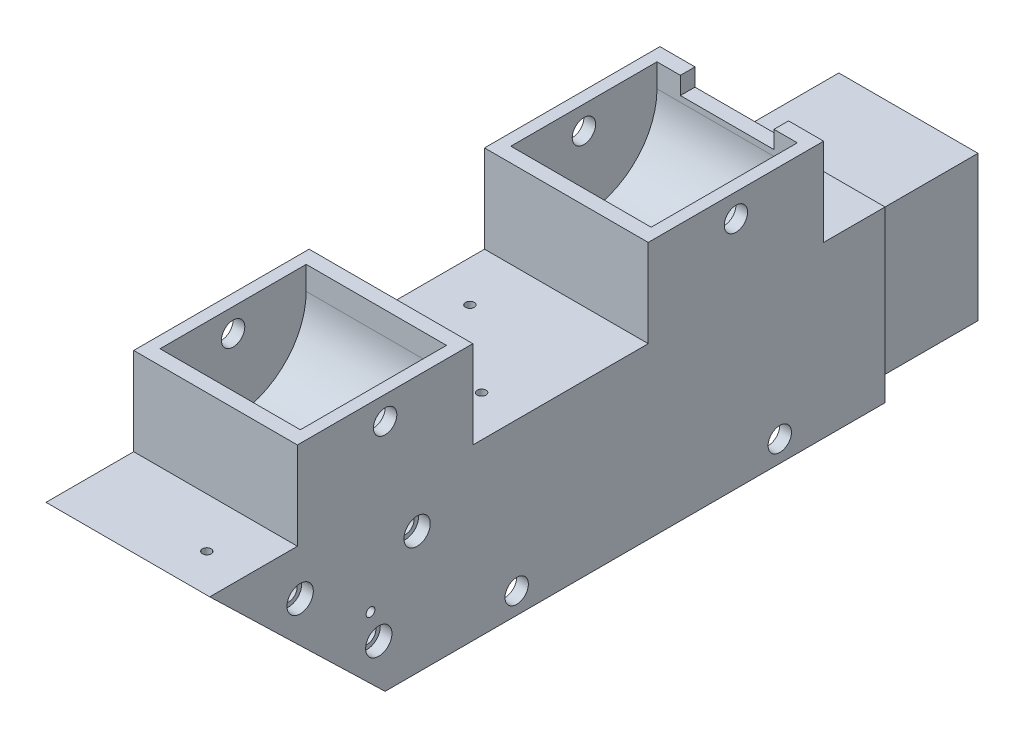
SolidWorks part; units mm, degrees
ref_plane "前视基准面" through (0, 0, 0) normal (0, 0, 1) x (1, 0, 0)
ref_plane "上视基准面" through (0, 0, 0) normal (0, 1, 0) x (1, 0, 0)
ref_plane "右视基准面" through (0, 0, 0) normal (1, 0, 0) x (0, 0, -1)
other "Configuration Table"
sketch "草图1" plane through (0, 0, 0) normal (1, 0, 0) x (0, 0, -1)
  line L0 (-150, 0) -> (150, 0) construction
  line L1 (-125, 14.5) -> (125, 14.5)
  line L2 (-125, 14.5) -> (-125, -14.5)
  line L3 (-125, -14.5) -> (125, -14.5)
  line L4 (125, 14.5) -> (125, -14.5)
  line L5 (-72.5, 29.5) -> (-72.5, 25.5)
  line L6 (-75, 14.5) -> (-45, 14.5)
  line L7 (-75, 14.5) -> (-75, 29.5)
  line L8 (-120, 10.8586) -> (120, 10.8586)
  line L9 (-120, 10.8586) -> (-120, -10.8586)
  line L10 (-120, -10.8586) -> (120, -10.8586)
  line L11 (120, 10.8586) -> (120, -10.8586)
  line L12 (-120, 10.8586) -> (120, -10.8586) construction
  line L13 (-120, -10.8586) -> (120, 10.8586) construction
  line L14 (-75, 29.5) -> (-45, 29.5)
  line L15 (-45, 14.5) -> (-45, 29.5)
  line L16 (-15, 14.5) -> (15, 14.5)
  line L17 (-15, 14.5) -> (-15, 29.5)
  line L18 (-15, 29.5) -> (15, 29.5)
  line L19 (15, 14.5) -> (15, 29.5)
  line L20 (45, 14.5) -> (75, 14.5)
  line L21 (45, 14.5) -> (45, 29.5)
  line L22 (45, 29.5) -> (75, 29.5)
  line L23 (75, 14.5) -> (75, 29.5)
  line L24 (-47.5, 29.5) -> (-47.5, 25.5)
  line L25 (-12.5, 29.5) -> (-12.5, 25.5)
  line L26 (12.5, 29.5) -> (12.5, 25.5)
  line L27 (47.5, 29.5) -> (47.5, 25.5)
  line L29 (72.5, 25.5) -> (72.5, 29.5)
  circle A2 centre (-67.5, -10.8586) radius 2
  circle A3 centre (-22.5, -10.8586) radius 2
  circle A4 centre (22.5, -10.8586) radius 2
  circle A5 centre (-60, 25.5) radius 2
  circle A6 centre (67.5, -10.8586) radius 2
  circle A7 centre (0, 25.5) radius 2
  circle A8 centre (60, 25.5) radius 2
  circle A9 centre (-60, 25.5) radius 12.5
  circle A10 centre (0, 25.5) radius 12.5
  circle A11 centre (60, 25.5) radius 12.5
  circle A12 centre (-67.5, -10.8586) radius 12.5
  circle A13 centre (-22.5, -10.8586) radius 12.5
  circle A14 centre (22.5, -10.8586) radius 12.5
  circle A15 centre (67.5, -10.8586) radius 12.5
  circle A16 centre (150, 0) radius 2
  circle A17 centre (-150, 0) radius 2
  circle A18 centre (-150, 0) radius 3.1
  point P10 (0, 0)
  point P12 (-125, 0)
  point P56 (-60, 29.5)
  point P62 (0, 29.5)
  point P64 (60, 29.5)
  dimension "D2" = 5
  dimension "D4" = 25
  dimension "D8" = 4
  dimension "D18" = 4
  dimension "D22" = 6.2
  dimension "D1" = 300
  dimension "D3" = 5
  dimension "D5" = 14.5
  dimension "D6" = 120
  dimension "D7" = 10.8586
  dimension "D9" = 52.5
  dimension "D10" = 45
  dimension "D11" = 45
  dimension "D12" = 45
  dimension "D13" = 60
  dimension "D14" = 60
  dimension "D15" = 60
  dimension "D16" = 60
  dimension "D17" = 52.5
  dimension "D19" = 30
  dimension "D20" = 4
  dimension "D21" = 15
extrude "凸台-拉伸1" add sketch "草图1" along normal blind 28 contours L1 L4 L3 L2 | L14 L15 L6 L7 | L18 L19 L16 L17 | L22 L23 L20 L21
extrude "切除-拉伸1" cut sketch "草图1<3>" along normal through all contours A2 | A3 | A4 | A6 | A8 | A7 | A5
sketch "草图1<3>" plane through (0, 0, 0) normal (1, 0, 0) x (0, 0, -1) same geometry as "草图1"
extrude "切除-拉伸2" cut sketch "草图1<5>" along normal offset from surface (24 mm away) 2 from offset 2 contours A9 L14 L5 | A9 L24 L14 | A10 L18 L25 | A10 L26 L18 | A11 L22 L27 | A11 L29 L22 | A12 | A9 | A13 | A10 | A14 | A11 | A15 region at (0, 28.5053, 72.3037) region at (0, 28.5053, 47.6963) region at (0, 28.5053, 12.3037) region at (0, 28.5053, -12.3037) region at (0, 28.5053, -47.6963) region at (0, 28.5053, -72.3037) up to face at (28, -10.8586, 65.5)
sketch "草图1<5>" plane through (0, 0, 0) normal (1, 0, 0) x (0, 0, -1) same geometry as "草图1"
sketch "草图3" plane through (0, 0, 125) normal (0, 0, 1) x (1, 0, 0)
  line L0 (28, 14.5) -> (28, -14.5) construction
  line L1 (28, 9.5) -> (22, 9.5)
  line L2 (28, 9.5) -> (28, -9.5)
  line L3 (28, -9.5) -> (22, -9.5)
  line L4 (22, 9.5) -> (22, -9.5)
  line L5 (28, 14.5) -> (0, 14.5) construction
  line L6 (28, -14.5) -> (0, -14.5) construction
  line L7 (0, 14.5) -> (0, -14.5) construction
  line L8 (0, 9.5) -> (6, 9.5)
  line L9 (0, 9.5) -> (0, -9.5)
  line L10 (0, -9.5) -> (6, -9.5)
  line L11 (6, 9.5) -> (6, -9.5)
  dimension "D1" = 6
  dimension "D2" = 5
  dimension "D3" = 5
extrude "凸台-拉伸2" add sketch "草图3" along normal blind 35 contours L1 L4 L3 L2
extrude "凸台-拉伸3" add sketch "草图3<3>" along normal blind 35 contours L2 L3 L4 L1 | L9 L10 L11 L8
sketch "草图3<3>" plane through (0, 0, 125) normal (0, 0, 1) x (1, 0, 0) same geometry as "草图3"
extrude "切除-拉伸3" cut sketch "草图1<6>" along normal through all contours A17
sketch "草图1<6>" plane through (0, 0, 0) normal (1, 0, 0) x (0, 0, -1) same geometry as "草图1"
extrude "切除-拉伸7" cut sketch "草图1<8>" along normal up to next contours A18
sketch "草图1<8>" plane through (0, 0, 0) normal (1, 0, 0) x (0, 0, -1) same geometry as "草图1"
fillet "圆角1" radius 9.5 4 edges at (25, 9.5, 160) (25, -9.5, 160) (3, -9.5, 160) (3, 9.5, 160)
fillet "圆角2" radius 5 2 edges at (14, -14.5, 125) (14, 14.5, 125)
sketch "草图4" plane through (0, 0, -125) normal (0, 0, -1) x (-1, 0, 0)
  line L1 (-28, 14.5) -> (0, 14.5) construction
  circle A0 centre (-14, 0) radius 5.1
  point P7 (-14, 14.5)
  dimension "D1" = 10.2
extrude "切除-拉伸4" cut sketch "草图4" against normal blind 31.5
extrude "切除-拉伸5" cut sketch "草图4<2>" against normal offset from surface (21.5 mm away) 10 flip side to cut up to face at (8.9, 0, -93.5)
sketch "草图4<2>" plane through (0, 0, -125) normal (0, 0, -1) x (-1, 0, 0) same geometry as "草图4"
sketch "草图5" plane through (0, 0, -103.5) normal (0, 0, -1) x (-1, 0, 0)
  line L0 (-28, 14.5) -> (0, 14.5) construction
  line L1 (-25.9, -12.4) -> (-2.1, -12.4)
  line L2 (-25.9, -12.4) -> (-25.9, 12.4)
  line L3 (-25.9, 12.4) -> (-2.1, 12.4)
  line L4 (-2.1, -12.4) -> (-2.1, 12.4)
  line L5 (-25.9, -12.4) -> (-2.1, 12.4) construction
  line L6 (-25.9, 12.4) -> (-2.1, -12.4) construction
  line L7 (0, -14.5) -> (0, 14.5) construction
  circle A0 centre (-14, 0) radius 5.1 construction
  point P0 (-14, 0)
  dimension "D1" = 2.1
  dimension "D2" = 2.1
extrude "切除-拉伸6" cut sketch "草图5" against normal blind 18 flip side to cut contours L3 L4 L1 L2
sketch "草图6" plane through (0, 14.5, 0) normal (0, 1, 0) x (1, 0, 0)
  circle A0 centre (7, 23.5) radius 0.75
  circle A1 centre (21, 35.5) radius 0.75
  circle A2 centre (7, -23.5) radius 0.75
  circle A3 centre (21, -35.5) radius 0.75
  dimension "D1" = 1.5
extrude "切除-拉伸8" cut sketch "草图6" against normal blind 4 contours A2 | A3 | A0 | A1
sketch "草图7" plane through (0, 14.5, 0) normal (0, 1, 0) x (1, 0, 0)
  circle A0 centre (7, -89.5) radius 0.75
  circle A1 centre (21.2, -110.5) radius 0.75
  dimension "D1" = 1.5
extrude "切除-拉伸9" cut sketch "草图7" against normal blind 4 contours A0 | A1
sketch "草图8" plane through (0, 0, 0) normal (-1, 0, 0) x (0, 0, 1)
  circle A0 centre (47, 4) radius 0.75
  circle A1 centre (2.499, -1.5) radius 0.75
  dimension "D1" = 1.5
extrude "切除-拉伸10" cut sketch "草图8" against normal blind 4
sketch "草图9" plane through (28, 0, 0) normal (1, 0, 0) x (0, 0, -1)
  circle A0 centre (-107.5, -0.5) radius 0.75
  circle A1 centre (-92.5, -0.5) radius 0.75
  dimension "D1" = 1.5
extrude "切除-拉伸11" cut sketch "草图9" against normal blind 4 contours A0 | A1
sketch "草图10" plane through (0, 0, 0) normal (-1, 0, 0) x (0, 0, 1)
  line L0 (30, 14.5) -> (0, -14.5)
  line L1 (45, 14.5) -> (15, 14.5) construction
  line L2 (120, -14.5) -> (-85.5, -14.5) construction
  line L3 (30, 14.5) -> (30, 45.5421)
  line L4 (30, 45.5421) -> (207.4503, 45.5421)
  line L5 (207.4503, 45.5421) -> (207.4503, -65.6361)
  line L6 (207.4503, -65.6361) -> (0, -65.6361)
  line L7 (0, -65.6361) -> (0, -14.5)
sketch "草图11" plane through (0, 0, 0) normal (1, 0, 0) x (0, 0, -1)
  line L0 (-30, 14.5) -> (0, -14.5) construction
  line L1 (-45, 14.5) -> (-15, 14.5) construction
  line L2 (-120, -14.5) -> (85.5, -14.5) construction
  circle A0 centre (-14.5301, 6.5) radius 0.75
  circle A1 centre (-1.0818, -6.5) radius 0.75
  circle A2 centre (-14.5301, 6.5) radius 2.25
  circle A3 centre (-1.0818, -6.5) radius 2.25
  circle A4 centre (-14.5301, 6.5) radius 1.5
  circle A5 centre (-1.0818, -6.5) radius 1.5
  circle A6 centre (5.4699, 6.5) radius 0.75
  circle A7 centre (5.4699, 6.5) radius 2.25
  circle A8 centre (5.4699, 6.5) radius 1.5
  dimension "D3" = 1.5
  dimension "D4" = 3
  dimension "D5" = 4.5
  dimension "D1" = 5
  dimension "D2" = 5
  dimension "D6" = 8
  dimension "D7" = 8
  dimension "D8" = 20
extrude "切除-拉伸12" cut sketch "草图11" along normal through all contours A1 | A0 | A6
extrude "切除-拉伸13" cut sketch "草图10" against normal through all
sketch "草图13" plane through (0, 0, 0) normal (0, 0, 1) x (1, 0, 0)
  line L0 (28, 14.5) -> (0, 14.5) construction
  line L1 (3.9, 10.6) -> (24.1, 10.6)
  line L2 (3.9, 10.6) -> (3.9, -10.6)
  line L3 (3.9, -10.6) -> (24.1, -10.6)
  line L4 (24.1, 10.6) -> (24.1, -10.6)
  line L5 (28, -14.5) -> (0, -14.5) construction
  line L6 (28, 14.5) -> (28, -14.5) construction
  line L7 (0, 45.5421) -> (0, -65.6361) construction
  dimension "D1" = 3.9
  dimension "D2" = 3.9
  dimension "D3" = 3.9
  dimension "D4" = 3.9
extrude "切除-拉伸14" cut sketch "草图13" against normal blind 40 from vertex starting at point (0, 14.5, 30)
extrude "切除-拉伸18" cut sketch "草图11<5>" along normal through all contours A4 | A8 | A5
sketch "草图11<5>" plane through (0, 0, 0) normal (1, 0, 0) x (0, 0, -1) same geometry as "草图11"
extrude "切除-拉伸19" cut sketch "草图11<6>" along normal blind 2 contours A7 | A3 | A2
sketch "草图11<6>" plane through (0, 0, 0) normal (1, 0, 0) x (0, 0, -1) same geometry as "草图11"
extrude "切除-拉伸20" cut sketch "草图11<7>" against normal blind 2 from surface contours A2 | A7 | A3 starting at face at (28, 6.5, 13.0301)
sketch "草图11<7>" plane through (0, 0, 0) normal (1, 0, 0) x (0, 0, -1) same geometry as "草图11"
sketch "草图15" plane through (0, 29.5, 0) normal (0, 1, 0) x (1, 0, 0)
  line L0 (26, 72.5) -> (2, 72.5) construction
  line L1 (6, 75) -> (22, 75)
  line L2 (6, 75) -> (6, 70)
  line L3 (6, 70) -> (22, 70)
  line L4 (22, 75) -> (22, 70)
  line L5 (6, 75) -> (22, 70) construction
  line L6 (6, 70) -> (22, 75) construction
  line L7 (28, 75) -> (0, 75) construction
  line L8 (2, 47.5) -> (2, 72.5) construction
  line L9 (6, 70) -> (22, 70)
  line L10 (6, 70) -> (6, 60)
  line L11 (6, 60) -> (22, 60)
  line L12 (22, 70) -> (22, 60)
  point P0 (14, 72.5)
  point P7 (14, 72.5)
  point P14 (2, 60)
  line M12 (28, 75) -> (0, 75)
  line M15 (2, 72.5) -> (26, 72.5)
  dimension "D1" = 16
extrude "切除-拉伸21" cut sketch "草图15" against normal blind 3 contours L4 L2 M12 M15 | L4 L2 L3 M15 | L12 L3 L10 L11 region at (14, 29.5, -73.75) region at (14, 29.5, -71.25) region at (14, 29.5, -65)
ref_plane "基准面1" through (-10, 0, 0) normal (1, 0, 0) x (0, 0, -1)
sketch "草图14" plane through (-10, 0, 0) normal (1, 0, 0) x (0, 0, -1)
  line L1 (-150, 50) -> (150, 50)
  line L2 (-150, 50) -> (-150, -50)
  line L3 (-150, -50) -> (150, -50)
  line L4 (150, 50) -> (150, -50)
  point P4 (-150, 0)
  point P6 (0, -50)
  dimension "D1" = 300
  dimension "D2" = 100
mirror "镜向1" about plane through (-10, 0, 0) normal (1, 0, 0) of bodies 154
extrude "切除-拉伸22" cut sketch "草图14" along normal through all
